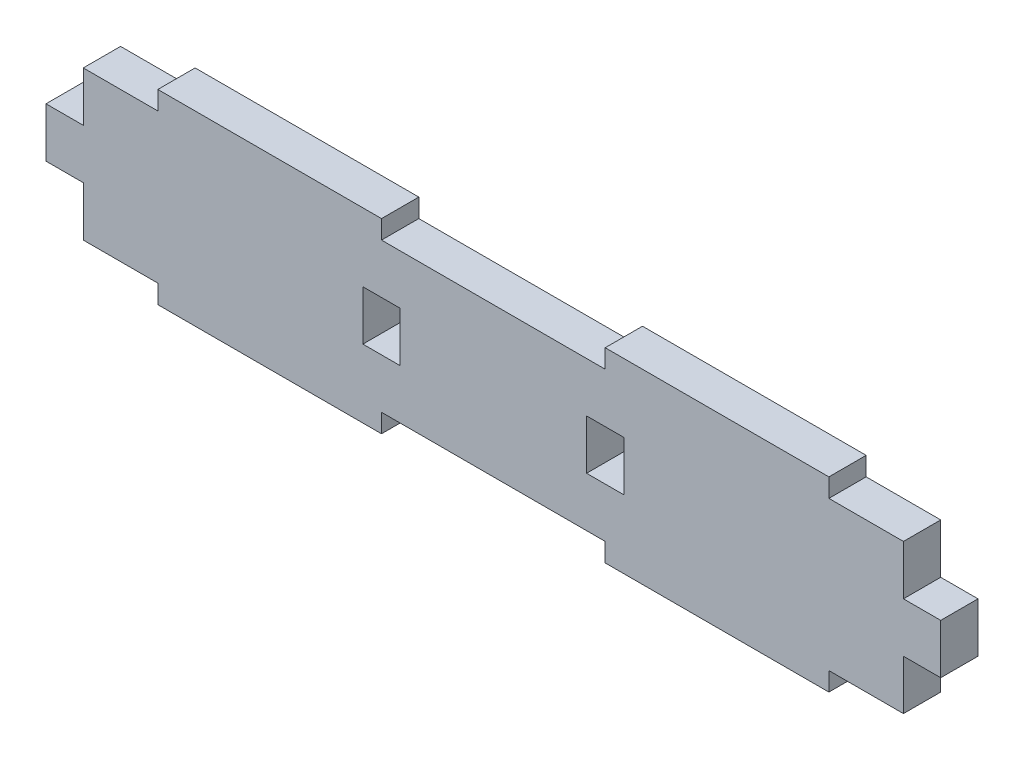
SolidWorks part; units mm, degrees
ref_plane "Front Plane" through (0, 0, 0) normal (0, 0, 1) x (1, 0, 0)
ref_plane "Top Plane" through (0, 0, 0) normal (0, 1, 0) x (1, 0, 0)
ref_plane "Right Plane" through (0, 0, 0) normal (1, 0, 0) x (0, 0, -1)
sketch "Sketch1" plane through (0, 0, 0) normal (0, 0, 1) x (1, 0, 0)
  line L1 (-152.4, -25.4) -> (152.4, -25.4)
  line L2 (-152.4, -25.4) -> (-152.4, 25.4)
  line L3 (-152.4, 25.4) -> (152.4, 25.4)
  line L4 (152.4, -25.4) -> (152.4, 25.4)
  line L5 (-152.4, -25.4) -> (152.4, 25.4) construction
  line L6 (-152.4, 25.4) -> (152.4, -25.4) construction
  point P0 (0, 0)
  dimension "D1" = 304.8
  dimension "D2" = 50.8
extrude "Boss-Extrude1" add sketch "Sketch1" along normal blind 12.7 contours L1 L3 region at (0, 0, 0)
sketch "Sketch2" plane through (0, 0, 12.7) normal (0, 0, 1) x (1, 0, 0)
  line L0 (-152.4, -25.4) -> (152.4, -25.4) construction
  line L1 (-38.1, -25.4) -> (-114.3, -25.4)
  line L2 (-38.1, -25.4) -> (-38.1, -31.75)
  line L3 (-38.1, -31.75) -> (-114.3, -31.75)
  line L4 (-114.3, -25.4) -> (-114.3, -31.75)
  line L5 (0, -6.985) -> (0, 6.985) construction
  line L6 (38.1, -31.75) -> (114.3, -31.75)
  line L7 (114.3, -25.4) -> (114.3, -31.75)
  line L8 (38.1, -25.4) -> (114.3, -25.4)
  line L9 (38.1, -25.4) -> (38.1, -31.75)
  line L10 (6.985, 0) -> (-6.985, 0) construction
  line L11 (38.1, 25.4) -> (38.1, 31.75)
  line L12 (38.1, 25.4) -> (114.3, 25.4)
  line L13 (114.3, 25.4) -> (114.3, 31.75)
  line L14 (38.1, 31.75) -> (114.3, 31.75)
  line L15 (-38.1, 31.75) -> (-114.3, 31.75)
  line L16 (-114.3, 25.4) -> (-114.3, 31.75)
  line L17 (-38.1, 25.4) -> (-114.3, 25.4)
  line L18 (-38.1, 25.4) -> (-38.1, 31.75)
  point P12 (-38.1, -28.575)
  dimension "D1" = 76.2
  dimension "D2" = 6.35
  dimension "D3" = 76.2
extrude "Boss-Extrude2" add sketch "Sketch2" against normal blind 12.7
sketch "Sketch3" plane through (0, 0, 12.7) normal (0, 0, 1) x (1, 0, 0)
  line L0 (6.985, 0) -> (-6.985, 0) construction
  line L1 (-152.4, -25.4) -> (-139.7, -25.4)
  line L2 (-152.4, -25.4) -> (-152.4, -8.4667)
  line L3 (-152.4, -8.4667) -> (-139.7, -8.4667)
  line L4 (-139.7, -25.4) -> (-139.7, -8.4667)
  line L5 (152.4, -25.4) -> (152.4, 25.4) construction
  line L6 (-152.4, 8.4667) -> (-139.7, 8.4667)
  line L7 (-139.7, 25.4) -> (-139.7, 8.4667)
  line L8 (-152.4, 25.4) -> (-139.7, 25.4)
  line L9 (-152.4, 25.4) -> (-152.4, 8.4667)
  line L10 (0, -6.985) -> (0, 6.985) construction
  line L11 (152.4, 25.4) -> (152.4, 8.4667)
  line L12 (152.4, 25.4) -> (139.7, 25.4)
  line L13 (139.7, 25.4) -> (139.7, 8.4667)
  line L14 (152.4, 8.4667) -> (139.7, 8.4667)
  line L15 (152.4, -8.4667) -> (139.7, -8.4667)
  line L16 (139.7, -25.4) -> (139.7, -8.4667)
  line L17 (152.4, -25.4) -> (139.7, -25.4)
  line L18 (152.4, -25.4) -> (152.4, -8.4667)
  line L19 (31.75, 8.4667) -> (44.45, 8.4667)
  line L20 (31.75, 8.4667) -> (31.75, -8.4667)
  line L21 (31.75, -8.4667) -> (44.45, -8.4667)
  line L22 (44.45, 8.4667) -> (44.45, -8.4667)
  line L23 (-38.1, -25.4) -> (38.1, -25.4) construction
  line L24 (-31.75, -8.4667) -> (-44.45, -8.4667)
  line L25 (-44.45, 8.4667) -> (-44.45, -8.4667)
  line L26 (-31.75, 8.4667) -> (-44.45, 8.4667)
  line L27 (-31.75, 8.4667) -> (-31.75, -8.4667)
  dimension "D1" = 16.9333
  dimension "D2" = 12.7
  dimension "D3" = 107.95
  dimension "D4" = 12.7
  dimension "D5" = 16.9333
  dimension "D6" = 16.9333
extrude "Cut-Extrude1" cut sketch "Sketch3" against normal through all
